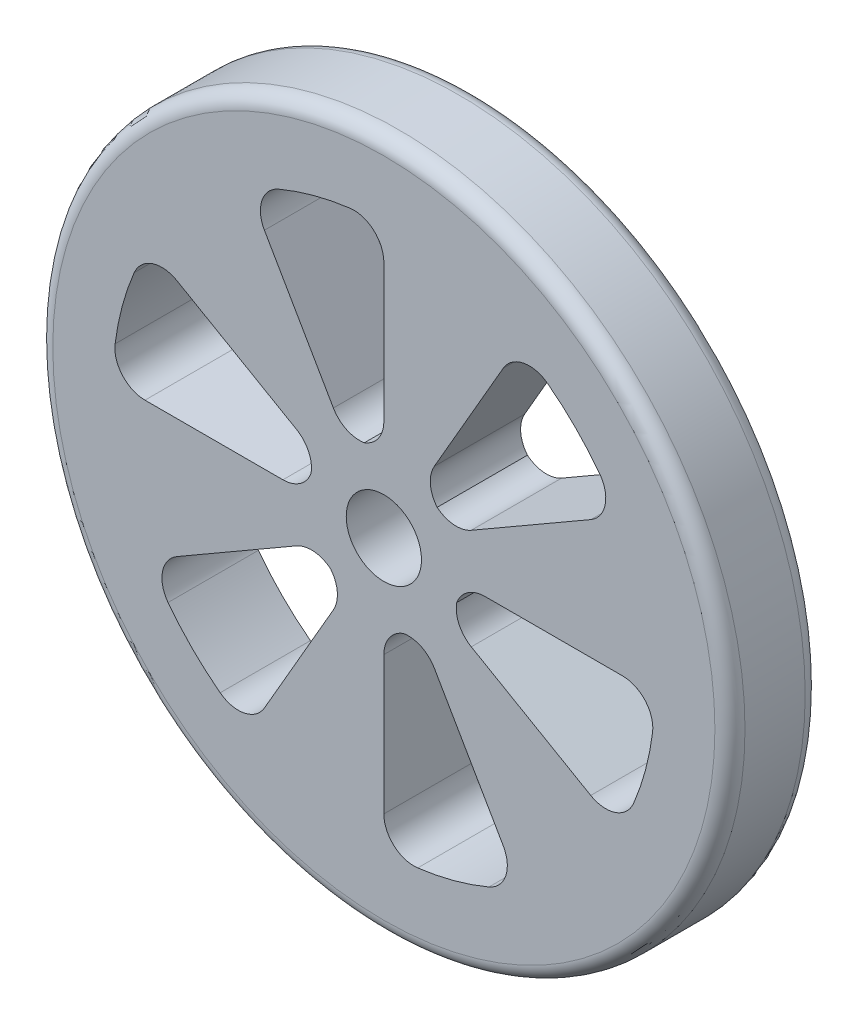
SolidWorks part; units mm, degrees
ref_plane "Front Plane" through (0, 0, 0) normal (0, 0, 1) x (1, 0, 0)
ref_plane "Top Plane" through (0, 0, 0) normal (0, 1, 0) x (1, 0, 0)
ref_plane "Right Plane" through (0, 0, 0) normal (1, 0, 0) x (0, 0, -1)
sketch "Sketch1" plane through (0, 0, 0) normal (0, 0, 1) x (1, 0, 0)
  circle A0 centre (0, 0) radius 23
  dimension "D1" = 46
extrude "Boss-Extrude1" add sketch "Sketch1" along normal blind 6
fillet "Fillet1" radius 1 2 edges at (23, 0, 0) (23, 0, 6)
sketch "Sketch2" plane through (0, 0, 0) normal (0, 0, -1) x (-1, 0, 0)
  line L0 (0, 18) -> (0, 5)
  line L1 (9, 15.5885) -> (2.5, 4.3301)
  line L2 (15.5885, 9) -> (4.3301, 2.5)
  line L3 (18, 0) -> (5, 0)
  line L4 (15.5885, -9) -> (4.3301, -2.5)
  line L5 (9, -15.5885) -> (2.5, -4.3301)
  line L6 (0, -18) -> (0, -5)
  line L7 (-9, -15.5885) -> (-2.5, -4.3301)
  line L8 (-15.5885, -9) -> (-4.3301, -2.5)
  line L9 (-18, 0) -> (-5, 0)
  line L10 (-15.5885, 9) -> (-4.3301, 2.5)
  line L11 (-9, 15.5885) -> (-2.5, 4.3301)
  arc A2 (-9, 15.5885) -> (-15.5885, 9) centre (0, 0) ccw
  arc A3 (-2.5, 4.3301) -> (-4.3301, 2.5) centre (0, 0) ccw
  arc A4 (-18, 0) -> (-15.5885, -9) centre (0, 0) ccw
  arc A5 (-5, 0) -> (-4.3301, -2.5) centre (0, 0) ccw
  arc A6 (9, 15.5885) -> (0, 18) centre (0, 0) ccw
  arc A7 (2.5, 4.3301) -> (0, 5) centre (0, 0) ccw
  arc A8 (5, 0) -> (4.3301, 2.5) centre (0, 0) ccw
  arc A9 (18, 0) -> (15.5885, 9) centre (0, 0) ccw
  arc A10 (2.5, -4.3301) -> (4.3301, -2.5) centre (0, 0) ccw
  arc A11 (9, -15.5885) -> (15.5885, -9) centre (0, 0) ccw
  arc A12 (-2.5, -4.3301) -> (0, -5) centre (0, 0) ccw
  arc A13 (-9, -15.5885) -> (0, -18) centre (0, 0) ccw
  dimension "D3" = 12
extrude "Cut-Extrude1" cut sketch "Sketch2" against normal through all
sketch "Sketch3" plane through (0, 0, 0) normal (0, 0, -1) x (-1, 0, 0)
  circle A1 centre (0, 0) radius 2.5
  dimension "D1" = 5
extrude "Cut-Extrude2" cut sketch "Sketch3" against normal blind 8
fillet "Fillet2" radius 2 24 edges at (9, 15.5885, 3) (15.5885, 9, 3) (2.5, 4.3301, 3) (4.3301, 2.5, 3) (15.5885, -9, 3) (18, 0, 3) (4.3301, -2.5, 3) (5, 0, 3) (0, -18, 3) (9, -15.5885, 3) (2.5, -4.3301, 3) (0, -5, 3) (-9, -15.5885, 3) (-2.5, -4.3301, 3) (-4.3301, -2.5, 3) (-15.5885, -9, 3) (-5, 0, 3) (-4.3301, 2.5, 3) (-18, 0, 3) (-15.5885, 9, 3) (0, 18, 3) (-9, 15.5885, 3) (0, 5, 3) (-2.5, 4.3301, 3)
